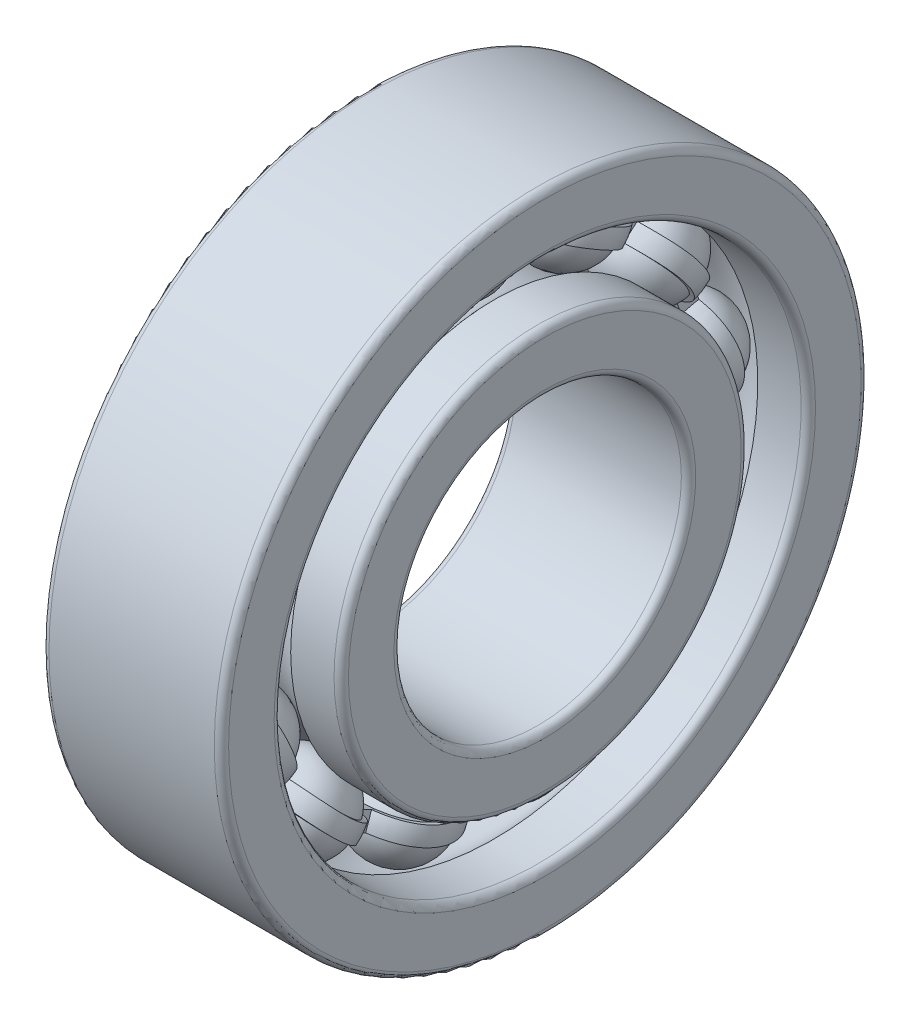
SolidWorks part; units mm, degrees
note: '?' marks a value the reader was unsure of.
material "AISI 304"
ref_plane "前视基准面" through (0, 0, 0) normal (0, 0, 1) x (1, 0, 0)
ref_plane "上视基准面" through (0, 0, 0) normal (0, 1, 0) x (1, 0, 0)
ref_plane "右视基准面" through (0, 0, 0) normal (1, 0, 0) x (0, 0, -1)
sketch "尺寸草图" plane through (0, 0, 0) normal (0, 0, 1) x (1, 0, 0)
  line L0 (-19.9271, 0) -> (19.9271, 0) construction
  line L1 (0, 21.603) -> (0, -21.603) construction
  line L2 (-1.15, 4.5) -> (1.15, 4.5)
  line L3 (1.25, 4.4) -> (1.25, 3.7667)
  line L4 (-1.25, 4.4) -> (-1.25, 3.7667)
  line L5 (-1.15, 3.6667) -> (1.15, 3.6667)
  line L6 (-3.5, 3.25) -> (3.3577, 3.25) construction
  line L7 (-1.15, 2.8333) -> (1.15, 2.8333)
  line L8 (1.25, 2.7333) -> (1.25, 2.1)
  line L9 (1.15, 2) -> (-1.15, 2)
  line L10 (-1.25, 2.1) -> (-1.25, 2.7333)
  line L11 (0, 3.25) -> (0, 3.875) construction
  circle A0 centre (0, 3.25) radius 0.625
  arc A1 (1.25, 3.7667) -> (1.15, 3.6667) centre (1.15, 3.7667) cw
  arc A2 (1.25, 2.7333) -> (1.15, 2.8333) centre (1.15, 2.7333) ccw
  arc A3 (-1.15, 2.8333) -> (-1.25, 2.7333) centre (-1.15, 2.7333) ccw
  arc A4 (-1.15, 3.6667) -> (-1.25, 3.7667) centre (-1.15, 3.7667) cw
  arc A5 (-1.15, 2) -> (-1.25, 2.1) centre (-1.15, 2.1) cw
  arc A6 (1.15, 2) -> (1.25, 2.1) centre (1.15, 2.1) ccw
  arc A7 (1.25, 4.4) -> (1.15, 4.5) centre (1.15, 4.4) ccw
  arc A8 (-1.15, 4.5) -> (-1.25, 4.4) centre (-1.15, 4.4) ccw
  point P7 (0, 0)
  point P25 (-1.25, 2.8333)
  point P28 (-1.25, 3.6667)
  point P31 (-1.25, 2)
  point P36 (1.25, 4.5)
  point P39 (-1.25, 4.5)
  dimension "D1" = 0.2083
  dimension "D3" = 0.1
  dimension "B" = 2.5
  dimension "D2" = 1.25
  dimension "D" = 9
  dimension "(d)" = 4
  dimension "D5" = 3.25
  dimension "D6" = 0.8333
  dimension "D7" = 0.8333
sketch "草图2" plane through (0, 0, 0) normal (0, 0, 1) x (1, 0, 0)
  line L6 (1.15, 2) -> (-1.15, 2) construction
  line L8 (-1.25, 4.4) -> (-1.25, 3.7667) construction
  line L9 (-1.15, 3.6667) -> (1.15, 3.6667) construction
  line L10 (-1.15, 4.5) -> (1.15, 4.5) construction
  line L11 (1.25, 4.4) -> (1.25, 3.7667) construction
  line L12 (1.25, 2.7333) -> (1.25, 2.1) construction
  line L13 (-1.15, 2.8333) -> (1.15, 2.8333) construction
  line L14 (1.15, 2) -> (-1.15, 2)
  line L15 (-1.25, 2.1) -> (-1.25, 2.7333) construction
  line L18 (-3.5, 0) -> (3.5, 0) construction
  line L19 (-19.9271, 0) -> (19.9271, 0) construction
  line L20 (-1.25, 4.4) -> (-1.25, 3.7667)
  line L21 (-1.15, 3.6667) -> (-0.4658, 3.6667)
  line L22 (-1.15, 4.5) -> (1.15, 4.5)
  line L23 (1.25, 4.4) -> (1.25, 3.7667)
  line L24 (1.25, 2.7333) -> (1.25, 2.1)
  line L25 (-1.15, 2.8333) -> (-0.4658, 2.8333)
  line L26 (-1.25, 2.1) -> (-1.25, 2.7333)
  line L27 (0.4658, 3.6667) -> (1.15, 3.6667)
  line L28 (0.4658, 2.8333) -> (1.15, 2.8333)
  circle A0 centre (0, 3.25) radius 0.625 construction
  arc A1 (0.4658, 3.6667) -> (-0.4658, 3.6667) centre (0, 3.25) ccw
  arc A2 (-0.4658, 2.8333) -> (0.4658, 2.8333) centre (0, 3.25) ccw
  arc A3 (-1.15, 4.5) -> (-1.25, 4.4) centre (-1.15, 4.4) ccw construction
  arc A4 (-1.25, 3.7667) -> (-1.15, 3.6667) centre (-1.15, 3.7667) ccw construction
  arc A5 (1.25, 4.4) -> (1.15, 4.5) centre (1.15, 4.4) ccw construction
  arc A6 (1.15, 3.6667) -> (1.25, 3.7667) centre (1.15, 3.7667) ccw construction
  arc A7 (1.25, 2.7333) -> (1.15, 2.8333) centre (1.15, 2.7333) ccw construction
  arc A8 (1.15, 2) -> (1.25, 2.1) centre (1.15, 2.1) ccw construction
  arc A9 (-1.15, 2.8333) -> (-1.25, 2.7333) centre (-1.15, 2.7333) ccw construction
  arc A10 (-1.25, 2.1) -> (-1.15, 2) centre (-1.15, 2.1) ccw construction
  arc A11 (-1.15, 4.5) -> (-1.25, 4.4) centre (-1.15, 4.4) ccw
  arc A12 (-1.25, 3.7667) -> (-1.15, 3.6667) centre (-1.15, 3.7667) ccw
  arc A13 (1.25, 4.4) -> (1.15, 4.5) centre (1.15, 4.4) ccw
  arc A14 (1.15, 3.6667) -> (1.25, 3.7667) centre (1.15, 3.7667) ccw
  arc A15 (1.25, 2.7333) -> (1.15, 2.8333) centre (1.15, 2.7333) ccw
  arc A16 (1.15, 2) -> (1.25, 2.1) centre (1.15, 2.1) ccw
  arc A17 (-1.15, 2.8333) -> (-1.25, 2.7333) centre (-1.15, 2.7333) ccw
  arc A18 (-1.25, 2.1) -> (-1.15, 2) centre (-1.15, 2.1) ccw
revolve "旋转1" add sketch "草图2" angle 360 about L18
sketch "草图5" plane through (0, 0, 0) normal (0, 0, 1) x (1, 0, 0)
  line L1 (-0.1875, 3.125) -> (0.1875, 3.125)
  line L2 (-0.1875, 3.125) -> (-0.1875, 3.375)
  line L3 (-0.1875, 3.375) -> (0.1875, 3.375)
  line L4 (0.1875, 3.125) -> (0.1875, 3.375)
  line L5 (-0.1875, 3.125) -> (0.1875, 3.375) construction
  line L6 (-0.1875, 3.375) -> (0.1875, 3.125) construction
  circle A0 centre (0, 3.25) radius 0.625 construction
  circle A1 centre (0, 3.25) radius 0.625 construction
  point P0 (0, 3.25)
  dimension "D1" = 0.375
  dimension "D2" = 0.25
revolve "旋转3" add sketch "草图5" angle 360 about L0
ref_axis "基准轴1" through (-3.85, 0, 0) along (1, 0, 0)?
sketch "草图3" plane through (0, 0, 0) normal (0, 0, 1) x (1, 0, 0)
  line L1 (-0.6875, 3.25) -> (0.6875, 3.25)
  circle A0 centre (0, 3.25) radius 0.625 construction
  circle A1 centre (0, 3.25) radius 0.625 construction
  arc A2 (0.6875, 3.25) -> (-0.6875, 3.25) centre (0, 3.25) ccw
  dimension "D2" = 1.375
revolve "旋转2" add sketch "草图3" angle 360 about L1
pattern_circular "阵列(圆周)5" count 13 over 360 about axis through (0, 0, 0) along (1, 0, 0) of bodies 103
sketch "草图6" plane through (0, 0, 0) normal (0, 0, 1) x (1, 0, 0)
  line L0 (-0.676, 3.375) -> (0.676, 3.375)
  line L1 (-3.5, 3.25) -> (1.25, 3.25) construction
  line L3 (-0.676, 3.125) -> (0.676, 3.125)
  line L4 (1.25, -4.4) -> (1.25, 4.4) construction
  arc A0 (-0.676, 3.125) -> (0.676, 3.125) centre (0, 3.25) ccw
  circle A1 centre (0, 3.25) radius 0.625 construction
  circle A2 centre (0, 3.25) radius 0.625 construction
  arc A3 (0.676, 3.375) -> (-0.676, 3.375) centre (0, 3.25) ccw
  dimension "D1" = 1.375
  dimension "D3" = 0.125
  dimension "D4" = 0.125
revolve "切除-旋转1" cut sketch "草图6" angle 360 about L0
sketch "草图7" plane through (0, 0, 0) normal (0, 0, 1) x (1, 0, 0)
  line L0 (-0.625, 3.25) -> (0.625, 3.25)
  line L1 (-1.25, 0) -> (1.25, 0) construction
  line L2 (-1.25, 4.4) -> (-1.25, -4.4) construction
  line L3 (1.25, -4.4) -> (1.25, 4.4) construction
  circle A0 centre (0, 3.25) radius 0.625 construction
  arc A1 (0.625, 3.25) -> (-0.625, 3.25) centre (0, 3.25) ccw
revolve "旋转4" add sketch "草图7" angle 360 about L0
pattern_circular "阵列(圆周)2" count 13 over 360 about axis through (0, 0, 0) along (1, 0, 0) of "旋转4"
